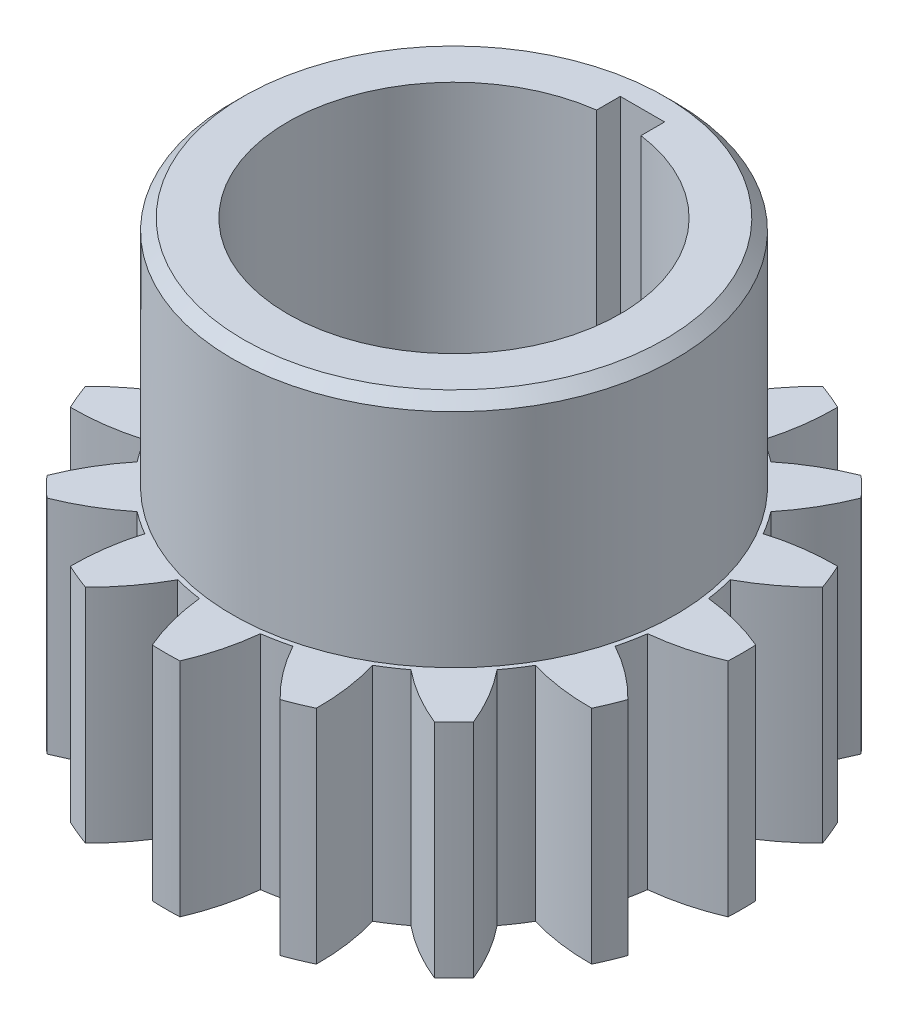
SolidWorks part; units mm, degrees
ref_plane "Front Plane" through (0, 0, 0) normal (0, 0, 1) x (1, 0, 0)
ref_plane "Top Plane" through (0, 0, 0) normal (0, 1, 0) x (1, 0, 0)
ref_plane "Right Plane" through (0, 0, 0) normal (1, 0, 0) x (0, 0, -1)
sketch "Sketch2" plane through (0, 0, 0) normal (0, 0, 1) x (1, 0, 0)
  line L0 (0, 0) -> (0, 25.4) construction
  line L1 (20.4, 20) -> (15, 20)
  line L2 (20.4, 20) -> (20.4, 0)
  line L3 (20.4, 0) -> (15, 0)
  line L4 (15, 20) -> (15, 0)
  line L5 (20.4, 20) -> (15, 0) construction
  line L6 (20.4, 0) -> (15, 20) construction
  line L8 (20, 41) -> (15, 41)
  line L9 (20, 41) -> (20, 20)
  line L10 (20, 20) -> (15, 20)
  line L11 (15, 41) -> (15, 20)
  line L12 (20, 41) -> (15, 20) construction
  line L13 (20, 20) -> (15, 41) construction
  point P0 (17.7, 10)
  point P5 (17.5, 30.5)
  dimension "D1" = 15
  dimension "D2" = 20.4
  dimension "D3" = 20
  dimension "D4" = 20
  dimension "D5" = 41
revolve "Revolve1" add sketch "Sketch2" angle 360 about L0 region at (17.7, 10, 0) region at (17.5, 30.5, 0)
ref_axis "Axis1" through (0, 41, 0) along (0, -1, 0)
sketch "Sketch4" plane through (0, 20, 0) normal (0, 1, 0) x (1, 0, 0)
  line L0 (0, 0) -> (0, 26) construction
  circle A0 centre (0, 0) radius 26
  circle A1 centre (0, 0) radius 20.4
  arc A2 (-1.25, 25.9699) -> (-2.75, 20.2138) centre (17.1385, 18.1045) ccw
  arc A3 (1.25, 25.9699) -> (2.75, 20.2138) centre (-17.1385, 18.1045) cw
  circle A4 centre (0, 0) radius 20.4 construction
  circle M5 centre (0, 0) radius 20.4
  dimension "D1" = 52
  dimension "D2" = 20
  dimension "D3" = 2.5
  dimension "D4" = 5.5
extrude "Boss-Extrude1" add sketch "Sketch4" against normal up to surface (20 mm away) contours L0 A0 A2 M5 | L0 A1 A3 A0 region at (-1.1221, 20, -22.8359) region at (1.1221, 20, -22.8359) up to face at (0, 0, -15)
pattern_circular "CirPattern1" count 16 over 360 about axis through (0, 41, 0) along (0, -1, 0) of "Boss-Extrude1"
sketch "Sketch6" plane through (0, 41, 0) normal (0, 1, 0) x (1, 0, 0)
  line L1 (-2, 17) -> (2, 17)
  line L2 (-2, 17) -> (-2, 13)
  line L3 (-2, 13) -> (2, 13)
  line L4 (2, 17) -> (2, 13)
  line L5 (-2, 17) -> (2, 13) construction
  line L6 (-2, 13) -> (2, 17) construction
  circle A0 centre (0, 0) radius 15 construction
  point P0 (0, 15)
  dimension "D1" = 4
extrude "Cut-Extrude1" cut sketch "Sketch6" against normal through all
chamfer "Chamfer1" distance 1 angle 45 1 edges at (0, 41, -20)
